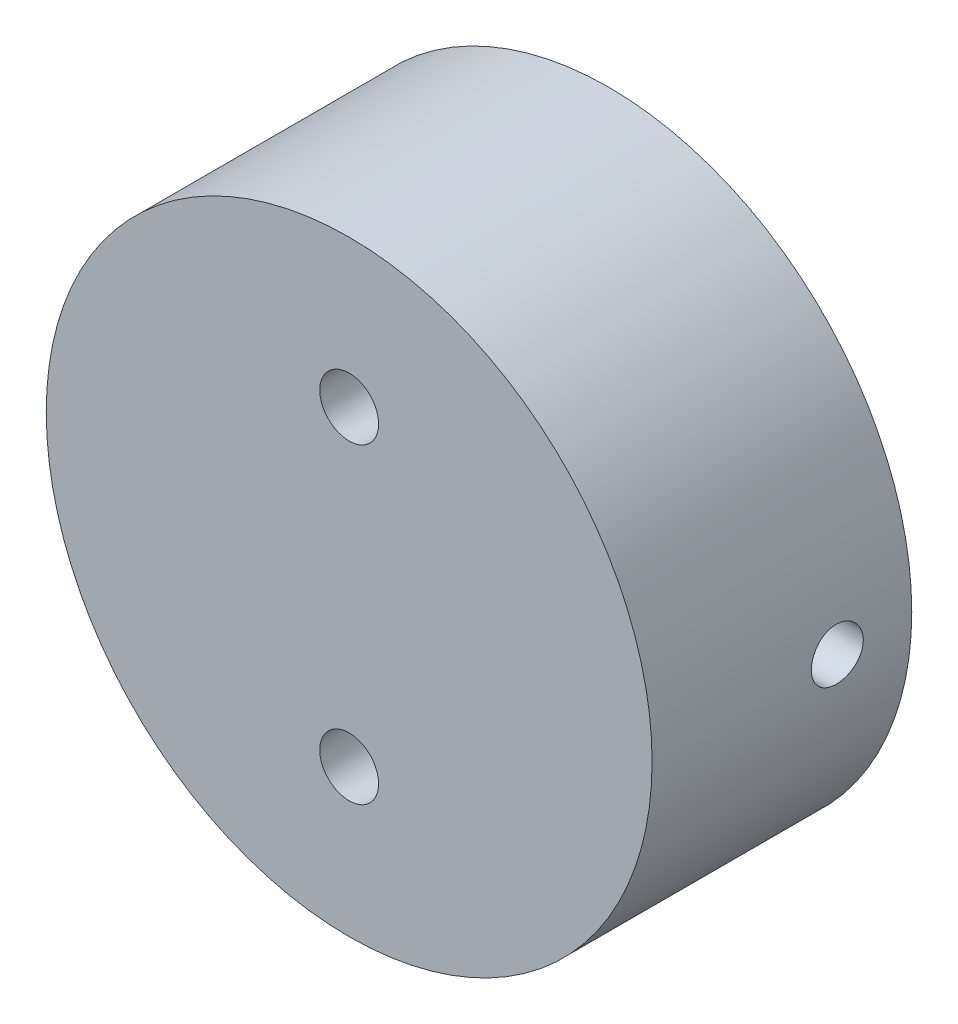
SolidWorks part; units mm, degrees
ref_plane "Front Plane" through (0, 0, 0) normal (0, 0, 1) x (1, 0, 0)
ref_plane "Top Plane" through (0, 0, 0) normal (0, 1, 0) x (1, 0, 0)
ref_plane "Right Plane" through (0, 0, 0) normal (1, 0, 0) x (0, 0, -1)
sketch "Sketch1" plane through (0, 0, 0) normal (0, 0, 1) x (1, 0, 0)
  line L1 (1.5877, 11.75) -> (-1.5877, 11.75)
  line L2 (-1.5877, 11.75) -> (-3.1754, 9)
  line L3 (-3.1754, 9) -> (-1.5877, 6.25)
  line L4 (-1.5877, 6.25) -> (1.5877, 6.25)
  line L5 (1.5877, 6.25) -> (3.1754, 9)
  line L6 (3.1754, 9) -> (1.5877, 11.75)
  line L7 (1.5877, -6.25) -> (-1.5877, -6.25)
  line L8 (-1.5877, -6.25) -> (-3.1754, -9)
  line L9 (-3.1754, -9) -> (-1.5877, -11.75)
  line L10 (-1.5877, -11.75) -> (1.5877, -11.75)
  line L11 (1.5877, -11.75) -> (3.1754, -9)
  line L12 (3.1754, -9) -> (1.5877, -6.25)
  circle A0 centre (0, 0) radius 2.5
  circle A2 centre (0, 0) radius 2.5 construction
  circle A3 centre (0, 0) radius 17.5
  circle A4 centre (0, 0) radius 9 construction
  circle A5 centre (0, 9) radius 2.75 construction
  circle A6 centre (0, -9) radius 2.75 construction
  point P7 (0, -9)
  point P8 (0, 9)
  dimension "D1" = 18
  dimension "D2" = 35
  dimension "D3" = 5.5
extrude "Boss-Extrude1" add sketch "Sketch1" against normal blind 10 contours A3 A0 region at (-17.005, 0, 0)
extrude "Boss-Extrude2" add sketch "Sketch1<3>" along normal blind 5 contours A3
sketch "Sketch1<3>" plane through (0, 0, 0) normal (0, 0, 1) x (1, 0, 0) same geometry as "Sketch1"
hole_wizard "M3 Clearance Hole1" positions "Sketch6" profile "Sketch7" hole size "M3" standard "ANSI Metric" end condition up to next
sketch "Sketch6" plane through (0, 0, 5) normal (0, 0, 1) x (1, 0, 0)
  point P0 (0, 9)
  point P2 (0, -9)
sketch "Sketch7" plane through (0, 9, 5) normal (1, 0, 0) x (0, -1, 0)
  line L0 (0, 0) -> (0, 5)
  line L1 (0, 5) -> (1.7, 5)
  line L2 (1.7, 5) -> (1.7, 0)
  line L5 (1.7, 0) -> (0, 0)
  line L11 (0, -6.35) -> (0, 107.95) construction
  dimension "Thru Hole Dia." = 3.4
  dimension "Thru Hole Depth" = 5
ref_plane "Plane1" through (2.5, 0, 0) normal (1, 0, 0) x (0, 0, -1)
ref_plane "Plane2" through (5.5, 0, 0) normal (1, 0, 0) x (0, 0, -1)
sketch "Sketch8" plane through (5.5, 0, 0) normal (1, 0, 0) x (0, 0, -1)
  line L0 (10, 0) -> (5.7, 0) construction
  line L1 (8.5, 2.8) -> (2.9, 2.8)
  line L3 (8.5, -2.8) -> (2.9, -2.8)
  line L4 (2.9, 2.8) -> (2.9, -2.8)
  line L5 (10, -17.5) -> (10, 17.5) construction
  line L6 (5.7, 2.8) -> (5.7, -2.8) construction
  line L7 (8.5, 2.8) -> (10, 2.8)
  line L8 (8.5, -2.8) -> (10, -2.8)
  line L9 (10, 2.8) -> (10, -2.8)
  circle A0 centre (5.7, 0) radius 1.5
  dimension "D4" = 3
  dimension "D1" = 5.6
  dimension "D2" = 5.6
  dimension "D3" = 1.5
extrude "Cut-Extrude1" cut sketch "Sketch8" along normal up to next and the other way up to next contours A0
extrude "Cut-Extrude2" cut sketch "Sketch8<4>" along normal blind 2.2 contours L1 L4 L3 L8 L9 L7
sketch "Sketch8<4>" plane through (5.5, 0, 0) normal (1, 0, 0) x (0, 0, -1) same geometry as "Sketch8"
ref_axis "Axis1" through (0, 0, -57.5) along (0, 0, 1)
ref_plane "Mirror Plane" through (0, 0, 0) normal (1, 0, 0) x (0, 0, -1)
mirror "Mirror1" about plane through (0, 0, 0) normal (1, 0, 0) of "Cut-Extrude2", "Cut-Extrude1"
